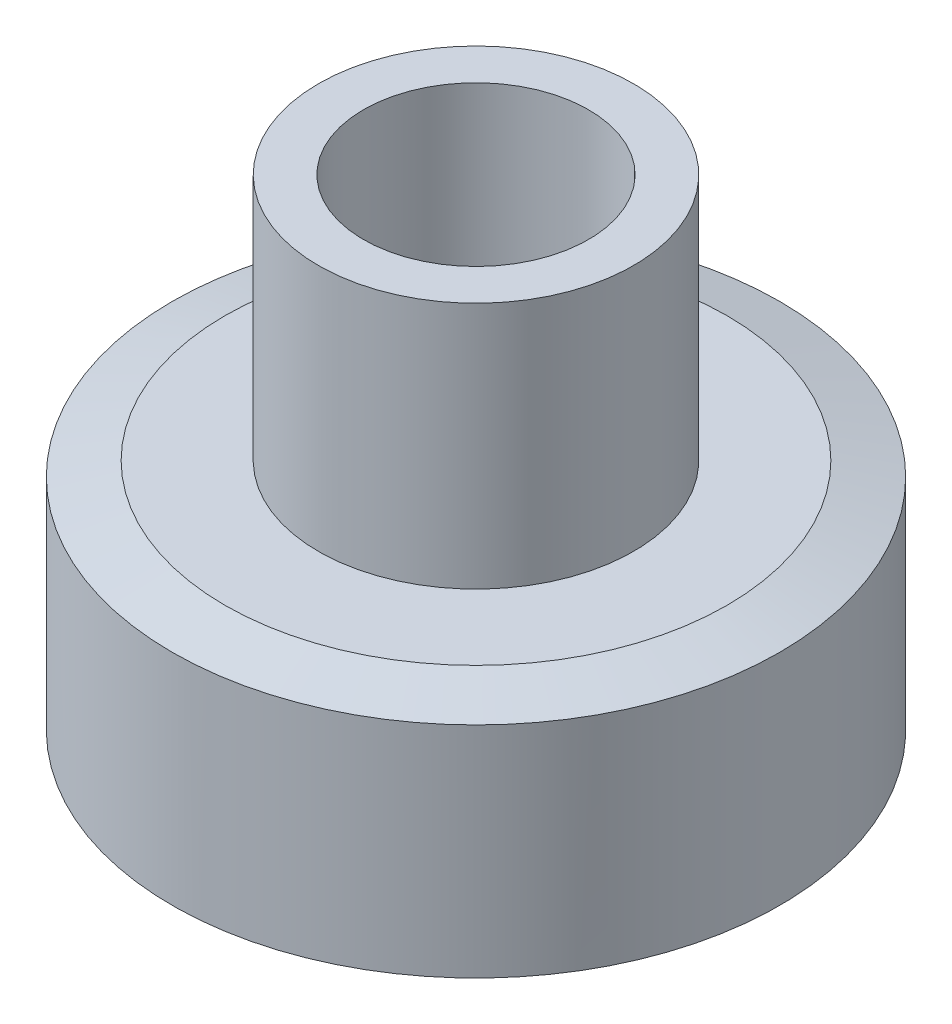
SolidWorks part; units mm, degrees
material "Сталь ШХ15 ГОСТ 801-78"
ref_plane "Plane1" through (0, 0, 0) normal (0, 0, 1) x (1, 0, 0)
ref_plane "Plane2" through (0, 0, 0) normal (0, 1, 0) x (1, 0, 0)
ref_plane "Plane3" through (0, 0, 0) normal (1, 0, 0) x (0, 0, -1)
sketch "Эскиз2" plane through (0, 0, 0) normal (0, 0, 1) x (1, 0, 0)
  line L0 (0, 0) -> (6.75, 0)
  line L1 (6.75, 0) -> (6.75, 5.5)
  line L2 (6.75, 5.5) -> (3.5, 5.5)
  line L3 (3.5, 5.5) -> (3.5, 11)
  line L4 (3.5, 11) -> (0, 11)
  line L5 (0, 11) -> (0, 0)
  dimension "D1" = 6.75
  dimension "D2" = 5.5
  dimension "D3" = 5.5
  dimension "D4" = 3.5
ref_axis "Ось1" through (0, 11, 0) along (0, -1, 0)
revolve "Повернуть2" add sketch "Эскиз2" angle 360 about axis through (0, 11, 0) along (0, -1, 0)
chamfer "Фаска2" distance 1.175 angle 15 1 edges at (-6.75, 5.5, 0) first distance on face at (-3.5, 5.5, 0)
chamfer "Фаска3" distance 1.175 angle 15 1 edges at (-6.75, 0, 0) first distance on face at (-6.75, 0, 0)
sketch "Эскиз3" plane through (0, 0, 0) normal (0, 0, 1) x (1, 0, 0)
  circle A0 centre (0, 8.027) radius 1
sketch "Эскиз4" plane through (0, 11, 0) normal (0, 1, 0) x (1, 0, 0)
  circle A0 centre (0, 0) radius 2.5
  dimension "D1" = 5
extrude "Вырез-Вытянуть2" cut sketch "Эскиз4" against normal through all both contours A0
